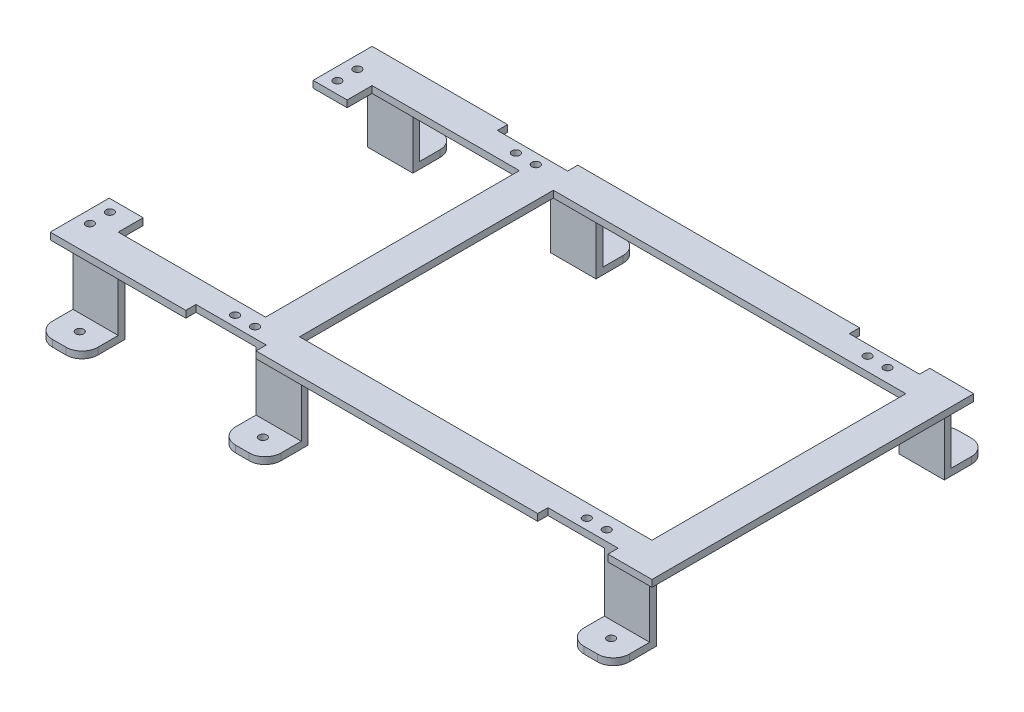
SolidWorks part; units mm, degrees
ref_plane "Alzado" through (0, 0, 0) normal (0, 0, 1) x (1, 0, 0)
ref_plane "Planta" through (0, 0, 0) normal (0, 1, 0) x (1, 0, 0)
ref_plane "Vista lateral" through (0, 0, 0) normal (1, 0, 0) x (0, 0, -1)
sketch "Croquis1" plane through (0, 0, 0) normal (0, 1, 0) x (1, 0, 0)
  line L0 (117.75, 56) -> (-117.75, 56)
  line L1 (132.75, -71) -> (-132.75, -71)
  line L2 (132.75, -71) -> (132.75, 71)
  line L3 (132.75, 71) -> (-132.75, 71)
  line L4 (-132.75, -71) -> (-132.75, 71)
  line L5 (132.75, -71) -> (-132.75, 71) construction
  line L6 (132.75, 71) -> (-132.75, -71) construction
  line L7 (-117.75, -56) -> (-117.75, 56)
  line L8 (117.75, -56) -> (-117.75, -56)
  line L9 (117.75, -56) -> (117.75, 56)
  point P0 (0, 0)
  dimension "D1" = 142
  dimension "D2" = 265.5
  dimension "D3" = 15
extrude "Saliente-Extruir1" add sketch "Croquis1" along normal blind 3
ref_plane "Plano1" through (-127.25, 0, 0) normal (1, 0, 0) x (0, 0, -1)
sketch "Croquis2" plane through (-127.25, 0, 0) normal (-1, 0, 0) x (0, 0, 1)
  line L0 (66.5, 0) -> (66.5, -26)
  line L6 (63.5, 0) -> (66.5, 0)
  line L8 (82.5, -29) -> (82.5, -26)
  line L9 (82.5, -26) -> (66.5, -26)
  line L20 (63.5, 0) -> (63.5, -29)
  line L21 (63.5, -29) -> (82.5, -29)
  line L22 (71, 3) -> (71, 0) construction
  line L23 (-71, 0) -> (71, 0) construction
  dimension "D1" = 29
  dimension "D2" = 3
  dimension "D3" = 4.5
  dimension "D4" = 19
  dimension "D5" = 3
extrude "Saliente-Extruir2" add sketch "Croquis2" against normal blind 20
mirror "Simetría1" about plane through (0, 0, 0) normal (1, 0, 0) of "Saliente-Extruir2"
mirror "Simetría2" about plane through (0, 0, 0) normal (0, 0, 1) of "Simetría1"
sketch "Croquis3" plane through (0, 3, 0) normal (0, 1, 0) x (1, 0, 0)
  line L1 (-120, 32.5) -> (-60, 32.5)
  line L2 (-120, 32.5) -> (-120, -32.5)
  line L3 (-120, -32.5) -> (-60, -32.5)
  line L4 (-60, 32.5) -> (-60, -32.5)
  point P4 (-60, 0)
  dimension "D1" = 65
  dimension "D2" = 60
  dimension "D3" = 60
extrude "Cortar-Extruir1" [suppressed] cut sketch "Croquis3" against normal through all
mirror "Simetría3" [suppressed] about plane through (0, 0, 0) normal (1, 0, 0)
ref_plane "Plano2" through (-36.45, 0, 0) normal (1, 0, 0) x (0, 0, -1)
sketch "Croquis4" plane through (-36.45, 0, 0) normal (1, 0, 0) x (0, 0, -1)
  line L12 (-63.5, 0) -> (-66.5, 0)
  line L13 (-66.5, 0) -> (-66.5, -26)
  line L14 (-66.5, -26) -> (-82.5, -26)
  line L15 (-82.5, -26) -> (-82.5, -29)
  line L16 (-82.5, -29) -> (-63.5, -29)
  line L17 (-82.5, -29) -> (-63.5, -29)
  line L19 (-66.5, 0) -> (-66.5, -26)
  line L20 (-66.5, -26) -> (-82.5, -26)
  line L21 (-82.5, -26) -> (-82.5, -29)
  line L28 (-63.5, 0) -> (-66.5, 0)
  line L38 (-63.5, -29) -> (-63.5, 0)
  line L40 (-63.5, -29) -> (-63.5, 0)
  dimension "D1" = 0
extrude "Saliente-Extruir3" add sketch "Croquis4" along normal mid plane 20
mirror "Simetría4" about plane through (0, 0, 0) normal (0, 0, 1) of "Saliente-Extruir3"
sketch "Croquis5" plane through (0, 3, 0) normal (0, 1, 0) x (1, 0, 0)
  line L1 (-105.499, -45) -> (-143.7054, -45)
  line L2 (-105.499, -45) -> (-105.499, 45)
  line L3 (-105.499, 45) -> (-143.7054, 45)
  line L4 (-143.7054, -45) -> (-143.7054, 45)
  line L5 (-105.499, -45) -> (-143.7054, 45) construction
  line L6 (-105.499, 45) -> (-143.7054, -45) construction
  point P0 (-124.6022, 0)
  dimension "D1" = 90
extrude "Cortar-Extruir2" cut sketch "Croquis5" against normal through all
sketch "Croquis7" plane through (0, 3, 0) normal (0, 1, 0) x (1, 0, 0)
  line L1 (-49.2, 56) -> (-23.2245, 56)
  line L2 (-49.2, 56) -> (-49.2, -56)
  line L3 (-49.2, -56) -> (-23.2245, -56)
  line L4 (-23.2245, 56) -> (-23.2245, -56)
extrude "Cortar-Extruir3" [suppressed] cut sketch "Croquis7" against normal through all
sketch "Croquis6" plane through (0, 3, 0) normal (0, 1, 0) x (1, 0, 0)
  line L0 (-45.25, 56) -> (-45.25, -56) construction
  line L1 (117.75, 56) -> (-117.75, 56) construction
  line L2 (-117.75, -56) -> (117.75, -56) construction
  line L3 (-132.75, 71) -> (-132.75, 45) construction
  line L6 (-52.75, 56) -> (-37.75, 56)
  line L7 (-52.75, 56) -> (-52.75, -56)
  line L8 (-52.75, -56) -> (-37.75, -56)
  line L9 (-37.75, 56) -> (-37.75, -56)
  point P12 (-45.25, 56)
  point P13 (-45.25, -56)
  dimension "D1" = 80
  dimension "D2" = 15
extrude "Saliente-Extruir4" add sketch "Croquis6" against normal up to surface (3 mm away) up to face at (-36.45, 0, -65)
sketch "Croquis8" plane through (0, 3, 0) normal (0, 1, 0) x (1, 0, 0)
  line L0 (132.75, 71) -> (-132.75, 71) construction
  line L1 (113.35, 66.5) -> (82.35, 66.5)
  line L2 (113.35, 66.5) -> (113.35, 71)
  line L3 (113.35, 71) -> (82.35, 71)
  line L4 (82.35, 66.5) -> (82.35, 71)
  line L5 (132.75, -71) -> (132.75, 71) construction
  line L6 (-132.75, 71) -> (-132.75, 45) construction
  line L7 (-41.95, 66.5) -> (-72.95, 66.5)
  line L8 (-41.95, 66.5) -> (-41.95, 71)
  line L9 (-41.95, 71) -> (-72.95, 71)
  line L10 (-72.95, 66.5) -> (-72.95, 71)
  dimension "D1" = 4.5
  dimension "D2" = 19.4
  dimension "D3" = 31
  dimension "D4" = 59.8
extrude "Cortar-Extruir4" cut sketch "Croquis8" against normal up to surface (3 mm away) up to face at (-70.1667, 0, 0)
sketch "Croquis9" plane through (0, 3, 0) normal (0, 1, 0) x (1, 0, 0)
  circle A0 centre (-127.25, 59) radius 1.75
  circle A1 centre (-127.25, 50.2) radius 1.75
extrude "Cortar-Extruir5" cut sketch "Croquis9" against normal through all
sketch "Croquis11" plane through (0, 3, 0) normal (0, 1, 0) x (1, 0, 0)
  circle A0 centre (103.7509, 61.953) radius 1.75
  circle A1 centre (94.9509, 61.953) radius 1.75
extrude "Cortar-Extruir7" cut sketch "Croquis11" against normal blind 4
sketch "Croquis12" plane through (0, 3, 0) normal (0, 1, 0) x (1, 0, 0)
  circle A0 centre (-51.4491, 61.953) radius 1.75
  circle A1 centre (-60.2491, 61.953) radius 1.75
  dimension "D1" = 3.5
extrude "Cortar-Extruir8" cut sketch "Croquis12" against normal blind 4
mirror "Simetría5" about plane through (0, 0, 0) normal (0, 0, 1) of "Cortar-Extruir8", "Cortar-Extruir7", "Cortar-Extruir5"
mirror "Simetría6" about plane through (0, 0, 0) normal (0, 0, 1) of "Cortar-Extruir4"
fillet "Redondeo1" radius 7 2 edges at (-127.25, -27.5, 82.5) (-107.25, -27.5, 82.5)
fillet "Redondeo2" radius 7 4 edges at (-26.45, -27.5, 82.5) (-46.45, -27.5, 82.5) (127.25, -27.5, 82.5) (107.25, -27.5, 82.5)
sketch "Croquis13" plane through (0, -26, 0) normal (0, 1, 0) x (1, 0, 0)
  line L0 (-114.25, -82.5) -> (-120.25, -82.5) construction
  line L1 (-127.25, -75.5) -> (-127.25, -66.5) construction
  circle A0 centre (-117.25, -73.5) radius 1.75
  dimension "D2" = 3.5
  dimension "D1" = 9
  dimension "D3" = 10
extrude "Cortar-Extruir9" cut sketch "Croquis13" against normal through all
mirror "Simetría7" about plane through (0, 0, 0) normal (1, 0, 0) of "Cortar-Extruir9"
sketch "Croquis15" plane through (0, -26, 0) normal (0, 1, 0) x (1, 0, 0)
  line L0 (-46.45, -66.5) -> (-46.45, -75.5) construction
  line L1 (-33.45, -82.5) -> (-39.45, -82.5) construction
  circle A0 centre (-36.45, -73.5) radius 1.75
  dimension "D3" = 3.5
  dimension "D1" = 10
  dimension "D2" = 9
extrude "Cortar-Extruir10" cut sketch "Croquis15" against normal through all
mirror "Simetría12" about plane through (0, 0, 0) normal (0, 0, 1) of "Cortar-Extruir10", "Simetría7", "Cortar-Extruir9"
fillet "Redondeo3" radius 7 6 edges at (-127.25, -27.5, -82.5) (-107.25, -27.5, -82.5) (-46.45, -27.5, -82.5) (-26.45, -27.5, -82.5) (107.25, -27.5, -82.5) (127.25, -27.5, -82.5)
